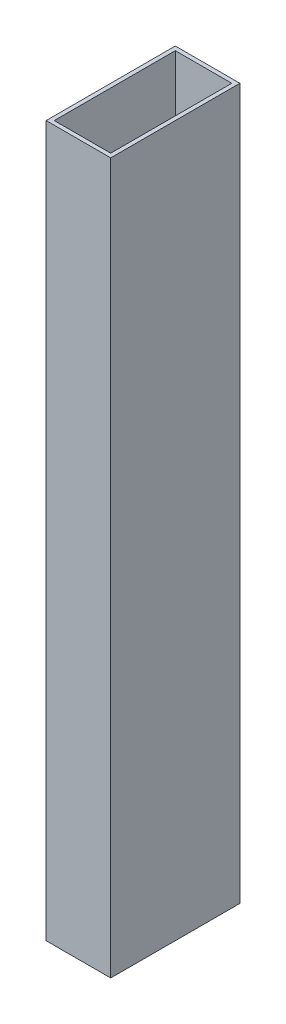
SolidWorks part; units mm, degrees
material "6061-T6 (SS)"
ref_plane "Front" through (0, 0, 0) normal (0, 0, 1) x (1, 0, 0)
ref_plane "Top" through (0, 0, 0) normal (0, 1, 0) x (1, 0, 0)
ref_plane "Right" through (0, 0, 0) normal (1, 0, 0) x (0, 0, -1)
sketch "Sketch1" plane through (0, 0, 0) normal (0, 1, 0) x (1, 0, 0)
  line L1 (12.7, 25.4) -> (-12.7, 25.4)
  line L2 (12.7, 25.4) -> (12.7, -25.4)
  line L3 (12.7, -25.4) -> (-12.7, -25.4)
  line L4 (-12.7, 25.4) -> (-12.7, -25.4)
  line L5 (12.7, 25.4) -> (-12.7, -25.4) construction
  line L6 (12.7, -25.4) -> (-12.7, 25.4) construction
  point P0 (0, 0)
  dimension "D1" = 25.4
  dimension "D2" = 50.8
extrude "Extrude-Thin1" add sketch "Sketch1" along normal up to surface (279.4 mm away) thin thin type one direction reverse wall 1.5875
